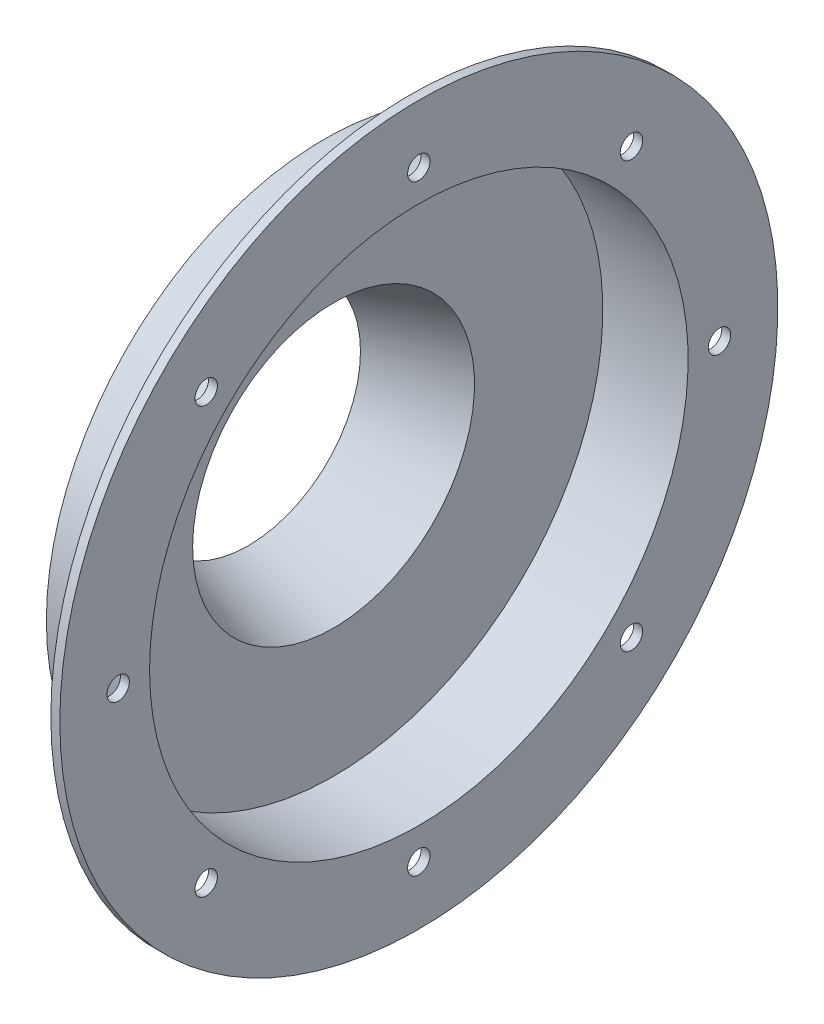
SolidWorks part; units mm, degrees
ref_plane "Front Plane" through (0, 0, 0) normal (0, 0, 1) x (1, 0, 0)
ref_plane "Top Plane" through (0, 0, 0) normal (0, 1, 0) x (1, 0, 0)
ref_plane "Right Plane" through (0, 0, 0) normal (1, 0, 0) x (0, 0, -1)
sketch "Sketch1" plane through (0, 0, 0) normal (0, 0, 1) x (1, 0, 0)
  line L0 (0, 0) -> (61.3012, 0) construction
  line L1 (0, 31.75) -> (24.13, 39.878)
  line L2 (24.13, 39.878) -> (24.13, 76.2)
  line L3 (24.13, 76.2) -> (48.26, 76.2)
  line L4 (48.26, 76.2) -> (48.26, 101.6)
  line L5 (-0.8108, 34.1571) -> (21.59, 41.7026)
  line L6 (21.59, 41.7026) -> (21.59, 78.74)
  line L7 (21.59, 78.74) -> (45.72, 78.74)
  line L8 (45.72, 78.74) -> (45.72, 101.6)
  line L9 (-0.8108, 34.1571) -> (0, 31.75)
  line L10 (45.72, 101.6) -> (48.26, 101.6)
  point P5 (30.6506, 0)
  dimension "D1" = 31.75
  dimension "D2" = 39.878
  dimension "D3" = 24.13
  dimension "D4" = 76.2
  dimension "D5" = 101.6
  dimension "D7" = 24.13
  dimension "D6" = 2.54
revolve "Revolve1" add sketch "Sketch1" angle 360 about L0
sketch "Sketch2" plane through (45.72, 0, 0) normal (-1, 0, 0) x (0, 0, 1)
  circle A0 centre (0, 85.09) radius 3.175
  dimension "D1" = 6.35
  dimension "D2" = 85.09
extrude "Cut-Extrude1" cut sketch "Sketch2" against normal blind 2.54
pattern_circular "CirPattern1" count 8 over 360 about axis through (45.72, 0, 0) along (-1, 0, 0) of "Cut-Extrude1"
